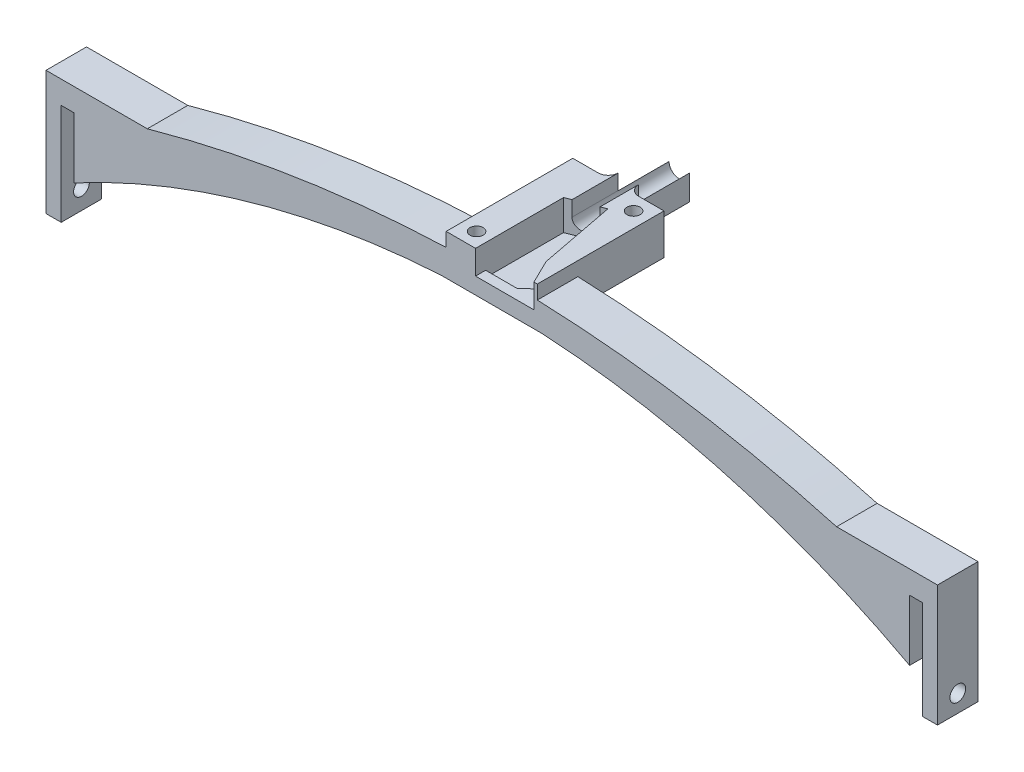
SolidWorks part; units mm, degrees
material "ABS"
ref_plane "Front Plane" through (0, 0, 0) normal (0, 0, 1) x (1, 0, 0)
ref_plane "Top Plane" through (0, 0, 0) normal (0, 1, 0) x (1, 0, 0)
ref_plane "Right Plane" through (0, 0, 0) normal (1, 0, 0) x (0, 0, -1)
sketch "Sketch1" plane through (0, 0, 0) normal (0, 0, 1) x (1, 0, 0)
  line L1 (0, 0) -> (2.5, 0) construction
  line L2 (0, 0) -> (0, 12) construction
  line L3 (0, 12) -> (2.5, 12) construction
  line L4 (2.5, 0) -> (2.5, 12) construction
  line L5 (167.5, 12) -> (170, 12) construction
  line L6 (167.5, 12) -> (167.5, 0) construction
  line L7 (167.5, 0) -> (170, 0) construction
  line L8 (170, 12) -> (170, 0) construction
  line L9 (-3, 0) -> (-3, 16.5)
  line L10 (-3, 16.5) -> (17, 16.5)
  line L11 (0, 0) -> (0, 12)
  line L12 (0, 12) -> (2.5, 12)
  line L13 (2.5, 12) -> (2.5, 0)
  line L14 (167.5, 12) -> (167.5, 0)
  line L15 (167.5, 12) -> (170, 12)
  line L16 (170, 12) -> (170.006, 12.0368)
  line L17 (170, 0) -> (170.006, 12.0368)
  line L19 (173, 0.5442) -> (173, 16.5)
  line L20 (173, 16.5) -> (153.0793, 16.5)
  line L21 (170, 0) -> (170, -7.4558)
  line L22 (170, -7.4558) -> (173, -7.4558)
  line L23 (173, -7.4558) -> (173, 0.5442)
  line L24 (-3, 16.5) -> (173, 16.5) construction
  line L25 (85, 16.5) -> (85, -29.5245) construction
  line L29 (-3, 0) -> (-3, -8)
  line L30 (-3, -8) -> (0, -8)
  line L31 (0, -8) -> (0, 0)
  line L32 (75, 20.4599) -> (95, 20.4599)
  arc A0 (2.5, 0) -> (75, 20.4599) centre (85, -153.6577) cw
  arc A1 (17, 16.5) -> (153.0793, 16.5) centre (85.0397, -225.6527) cw
  arc A2 (95, 20.4599) -> (167.5, 0) centre (85, -153.6577) cw
  dimension "D6" = 3
  dimension "D1" = 2.5
  dimension "D2" = 2.5
  dimension "D3" = 165
  dimension "D4" = 12
  dimension "D5" = 12
  dimension "D7" = 20
  dimension "D8" = 8
  dimension "D9" = 8
  dimension "D10" = 3
  dimension "D11" = 20
  dimension "D12" = 10
  dimension "D13" = 3
  dimension "D14" = 4.5
extrude "Boss-Extrude1" add sketch "Sketch1" along normal blind 8
sketch "Sketch2" plane through (-3, 0, 0) normal (-1, 0, 0) x (0, 0, 1)
  line L1 (0, 16.5) -> (0, -8) construction
  line L2 (8, 16.5) -> (0, 16.5) construction
  circle A0 centre (4, -4) radius 1.55
  dimension "D1" = 3.1
  dimension "D2" = 20.5
  dimension "D3" = 4
extrude "Cut-Extrude1" cut sketch "Sketch2" against normal through all contours A0
sketch "Sketch3" plane through (0, 0, 0) normal (0, 1, 0) x (1, 0, 0)
  line L5 (94, 17) -> (87, 17)
  line L6 (94, 17) -> (94, -8)
  line L7 (94, -8) -> (76, -8)
  line L8 (76, 17) -> (76, -8)
  line L9 (173, -8) -> (173, 0) construction
  line L12 (83, 17) -> (76, 17)
  line L14 (83, 17) -> (83, 29)
  line L15 (83, 29) -> (87, 29)
  line L16 (87, 17) -> (87, 29)
  circle A0 centre (91, 14) radius 1.3
  circle A1 centre (79, -5) radius 1.3
  dimension "D4" = 2.6
  dimension "D7" = 2.6
  dimension "D1" = 18
  dimension "D2" = 25
  dimension "D3" = 79
  dimension "D5" = 4
  dimension "D6" = 7
  dimension "D8" = 3
  dimension "D9" = 3
  dimension "D10" = 3
  dimension "D11" = 3
  dimension "D12" = 12
extrude "Boss-Extrude3" add sketch "Sketch3" along normal blind 8 from surface starting at face at (85, 20.4599, 4)
sketch "Sketch5" plane through (0, 0, 8) normal (0, 0, 1) x (1, 0, 0)
  line L0 (95, 20.4599) -> (75, 20.4599) construction
  line L3 (82.9995, 25.4599) -> (82.9995, 28.4599)
  line L4 (94, 28.4599) -> (76, 28.4599) construction
  line L5 (82.9995, 28.4599) -> (87.0005, 28.4599)
  line L6 (87.0005, 28.4599) -> (87.0005, 25.4599)
  line L7 (-3, 16.5) -> (173, 16.5) construction
  line L8 (85, 16.5) -> (85, 43.7245) construction
  arc A0 (82.9995, 25.4599) -> (87.0005, 25.4599) centre (85, 25.4599) ccw
  dimension "D1" = 4.001
  dimension "D2" = 5
extrude "Cut-Extrude2" cut sketch "Sketch5" against normal blind 40 from offset 2 offset against normal yes
extrude "Cut-Extrude3" cut sketch "Sketch3<3>" against normal through all both and the other way through all contours A1 region at (79, 0, 5)
sketch "Sketch3<3>" plane through (0, 0, 0) normal (0, 1, 0) x (1, 0, 0) same geometry as "Sketch3"
sketch "Sketch6" plane through (0, 28.4599, 0) normal (0, 1, 0) x (1, 0, 0)
  line L0 (81.7995, 9.38) -> (88.1135, 11.8088)
  line L1 (88.1135, 11.8088) -> (91.0245, -3.2881)
  line L2 (91.0245, -3.2881) -> (87.9495, -6)
  line L3 (87.9495, -6) -> (81.7995, -6)
  line L4 (81.7995, -6) -> (81.7995, 9.38)
  line L5 (87.0005, -6) -> (82.9995, -6) construction
  line L7 (82.9995, 17) -> (82.9995, -6) construction
  dimension "D1" = 6.765
  dimension "D2" = 6.15
  dimension "D3" = 15.375
  dimension "D4" = 4.1
  dimension "D5" = 9.225
  dimension "D6" = 1.2
  dimension "D7" = 15.38
extrude "Cut-Extrude4" cut sketch "Sketch6" against normal blind 6
sketch "Sketch7" plane through (0, 28.4599, 0) normal (0, 1, 0) x (1, 0, 0)
  line L0 (91.0245, -3.2881) -> (93.3288, -8)
  line L1 (94, -8) -> (76, -8) construction
  line L2 (93.3288, -8) -> (81.7995, -8)
  line L3 (81.7995, -8) -> (81.7995, -6)
  line L4 (81.7995, -6) -> (87.9495, -6)
  line L5 (87.9495, -6) -> (91.0245, -3.2881)
  dimension "D1" = 90
  dimension "D2" = 2
  dimension "D3" = 11.5293
  dimension "D4" = 6.15
  dimension "D5" = 4.1
  dimension "D6" = 5.2452
  dimension "D7" = 74.651
extrude "Cut-Extrude5" cut sketch "Sketch7" against normal blind 4.75
fillet "Fillet1" radius 2 2 edges at (87, 22.9375, -17) (83, 22.9375, -17)
